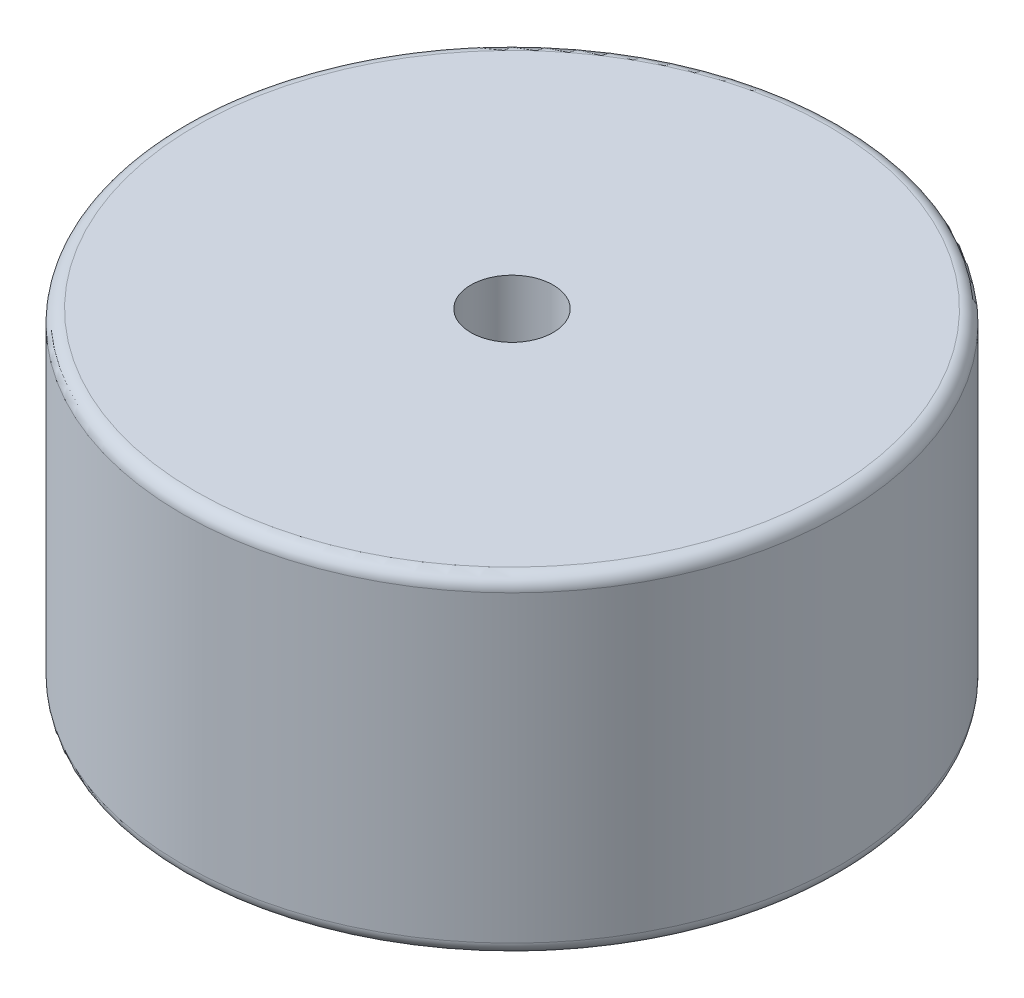
SolidWorks part; units mm, degrees
material "6061 Alloy"
ref_plane "Front" through (0, 0, 0) normal (0, 0, 1) x (1, 0, 0)
ref_plane "Top" through (0, 0, 0) normal (0, 1, 0) x (1, 0, 0)
ref_plane "Right" through (0, 0, 0) normal (1, 0, 0) x (0, 0, -1)
sketch "Sketch1" plane through (0, 0, 0) normal (0, 1, 0) x (1, 0, 0)
  circle A0 centre (0, 0) radius 20
  dimension "D1" = 40
extrude "Boss-Extrude1" add sketch "Sketch1" along normal blind 20
sketch "Sketch2" plane through (0, 20, 0) normal (0, 1, 0) x (1, 0, 0)
  circle A0 centre (0, 0) radius 2.5
  dimension "D1" = 5
extrude "Cut-Extrude1" cut sketch "Sketch2" against normal blind 12
fillet "Fillet1" radius 0.7937 2 edges at (0, 0, 20) (0, 20, 20)
sketch "Sketch3" plane through (0, 0, 0) normal (0, -1, 0) x (1, 0, 0)
  circle A0 centre (0, 0) radius 9
  circle A1 centre (0, 0) radius 17
  circle A2 centre (0, 0) radius 20 construction
  dimension "D1" = 18
  dimension "D2" = 3
extrude "Cut-Extrude2" cut sketch "Sketch3" against normal blind 0.7937 contours A1 A0 region at (-16.5192, 0, 0)
